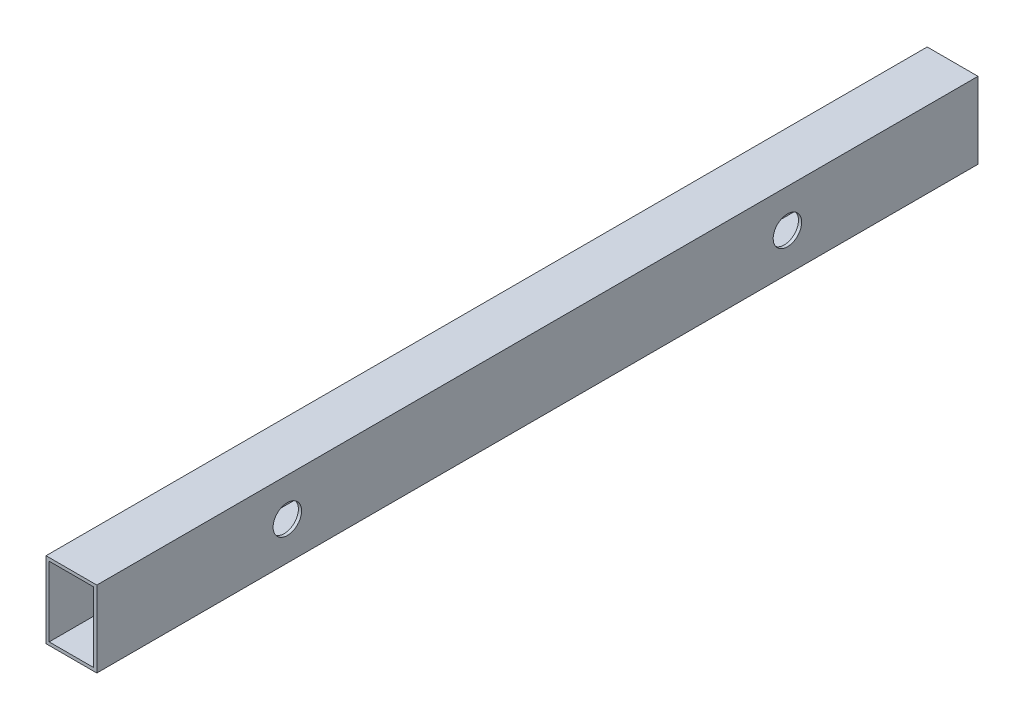
SolidWorks part; units mm, degrees
ref_plane "Front Plane" through (0, 0, 0) normal (0, 0, 1) x (1, 0, 0)
ref_plane "Top Plane" through (0, 0, 0) normal (0, 1, 0) x (1, 0, 0)
ref_plane "Right Plane" through (0, 0, 0) normal (1, 0, 0) x (0, 0, -1)
sketch "Sketch1" plane through (0, 0, 0) normal (0, 0, 1) x (1, 0, 0)
  line L0 (0, 38.1) -> (0, 34.925) construction
  line L1 (-25.4, 38.1) -> (25.4, 38.1)
  line L2 (-25.4, 38.1) -> (-25.4, -38.1)
  line L3 (-25.4, -38.1) -> (25.4, -38.1)
  line L4 (25.4, 38.1) -> (25.4, -38.1)
  line L5 (-25.4, 38.1) -> (25.4, -38.1) construction
  line L6 (-25.4, -38.1) -> (25.4, 38.1) construction
  line L7 (-22.225, 34.925) -> (22.225, 34.925)
  line L8 (-22.225, 34.925) -> (-22.225, -34.925)
  line L9 (-22.225, -34.925) -> (22.225, -34.925)
  line L10 (22.225, 34.925) -> (22.225, -34.925)
  line L11 (22.225, 0) -> (25.4, 0) construction
  line L12 (-22.225, 0) -> (-25.4, 0) construction
  line L13 (0, -34.925) -> (0, -38.1) construction
  point P0 (0, 0)
  dimension "D1" = 76.2
  dimension "D2" = 50.8
  dimension "D3" = 3.175
extrude "Boss-Extrude1" add sketch "Sketch1" along normal blind 965.2
sketch "Sketch2" plane through (0, 38.1, 0) normal (0, 1, 0) x (1, 0, 0)
  line L0 (-26.9875, -190.549) -> (26.9875, -190.549) construction
  line L1 (-25.4, 0) -> (25.4, 0)
  line L2 (-25.4, 0) -> (-25.4, -965.2)
  line L3 (-25.4, -965.2) -> (25.4, -965.2)
  line L4 (25.4, 0) -> (25.4, -965.2)
  line L5 (-26.4963, -703.2466) -> (26.4963, -703.2466) construction
  line L6 (0, -703.2466) -> (0, -190.549) construction
  line L7 (0, 0) -> (0, -190.549) construction
  line L8 (-74.6125, -402.6047) -> (-73.6301, -528.6965) construction
  line L9 (-74.1213, -465.6506) -> (-23.8125, -465.6506) construction
  line L10 (-23.8125, -465.6506) -> (26.9875, -465.6506) construction
  dimension "D1" = 190.549
  dimension "D2" = 512.6976
  dimension "D3" = 126.0917
  dimension "D4" = 50.3088
  dimension "D5" = 50.8
  dimension "D6" = 53.975
  dimension "D7" = 52.9926
  dimension "D8" = 275.1016
ref_plane "Plane1" through (25.4, 0, 0) normal (1, 0, 0) x (0, 0, -1)
sketch "Sketch4" plane through (25.4, 0, 0) normal (1, 0, 0) x (0, 0, -1)
  line L0 (-690.548, 38.1) -> (-690.548, 0) construction
  line L1 (-703.2466, 38.1) -> (-190.549, 38.1) construction
  line L2 (-190.549, 38.1) -> (-190.549, 0) construction
  line L3 (0, 38.1) -> (-190.549, 38.1) construction
  line L4 (-190.549, 0) -> (0, 0) construction
  line L5 (0, -38.1) -> (0, 38.1) construction
  line L6 (-190.549, 0) -> (-690.548, 0) construction
  circle A0 centre (-690.548, 0) radius 14.224
  circle A1 centre (-190.549, 0) radius 14.224
  dimension "D1" = 28.448
  dimension "D2" = 499.999
  dimension "D3" = 190.549
extrude "Cut-Extrude1" cut sketch "Sketch4" against normal up to surface (50.8 mm away) contours A1 | A0 up to face at (-25.4, 0, 482.6)
sketch "Sketch5" plane through (0, -38.1, 0) normal (0, -1, 0) x (1, 0, 0)
  line L0 (0, 0) -> (0, 283.21) construction
  line L1 (0, 283.21) -> (-25.4, 283.21) construction
  line L2 (-25.4, 965.2) -> (-25.4, 0) construction
  line L3 (-19.05, 283.21) -> (-19.05, 276.86) construction
  line L4 (-19.05, 283.21) -> (-19.05, 289.56) construction
  line L5 (-19.05, 289.56) -> (0, 289.56) construction
  line L6 (0, 289.56) -> (0, 410.718) construction
  line L7 (0, 410.718) -> (0, 580.898) construction
  circle A0 centre (-19.05, 276.86) radius 3.175
  circle A1 centre (-19.05, 289.56) radius 3.175
  circle A2 centre (19.05, 276.86) radius 3.175
  circle A3 centre (19.05, 289.56) radius 3.175
  circle A4 centre (0, 410.718) radius 3.175
  circle A5 centre (0, 580.898) radius 3.175
  circle A6 centre (0, 495.808) radius 3.175
  dimension "D5" = 6.35
  dimension "D8" = 6.35
  dimension "D1" = 283.21
  dimension "D2" = 6.35
  dimension "D3" = 6.35
  dimension "D4" = 6.35
  dimension "D6" = 121.158
  dimension "D7" = 170.18
extrude "Cut-Extrude2" cut sketch "Sketch5" against normal up to surface (3.175 mm away) up to face at (0, -34.925, 482.6)
sketch "Sketch6" plane through (25.4, 0, 0) normal (1, 0, 0) x (0, 0, -1)
  line L0 (0, 0) -> (-190.549, 0) construction
  line L1 (-690.548, 0) -> (-881.048, 0) construction
  line L2 (-881.048, 0) -> (-881.048, -38.1) construction
  line L3 (-965.2, -38.1) -> (0, -38.1) construction
  line L4 (-881.048, 0) -> (-881.048, 38.1) construction
  line L5 (-965.2, 38.1) -> (0, 38.1) construction
  line L7 (-881.048, 38.1) -> (-965.2, 38.1)
  line L8 (-881.048, 38.1) -> (-881.048, -38.1)
  line L9 (-881.048, -38.1) -> (-965.2, -38.1)
  line L10 (-965.2, 38.1) -> (-965.2, -38.1)
  dimension "D1" = 190.5
extrude "Cut-Extrude3" cut sketch "Sketch6" against normal up to surface (50.8 mm away) up to face at (-25.4, 14.224, 190.549)
